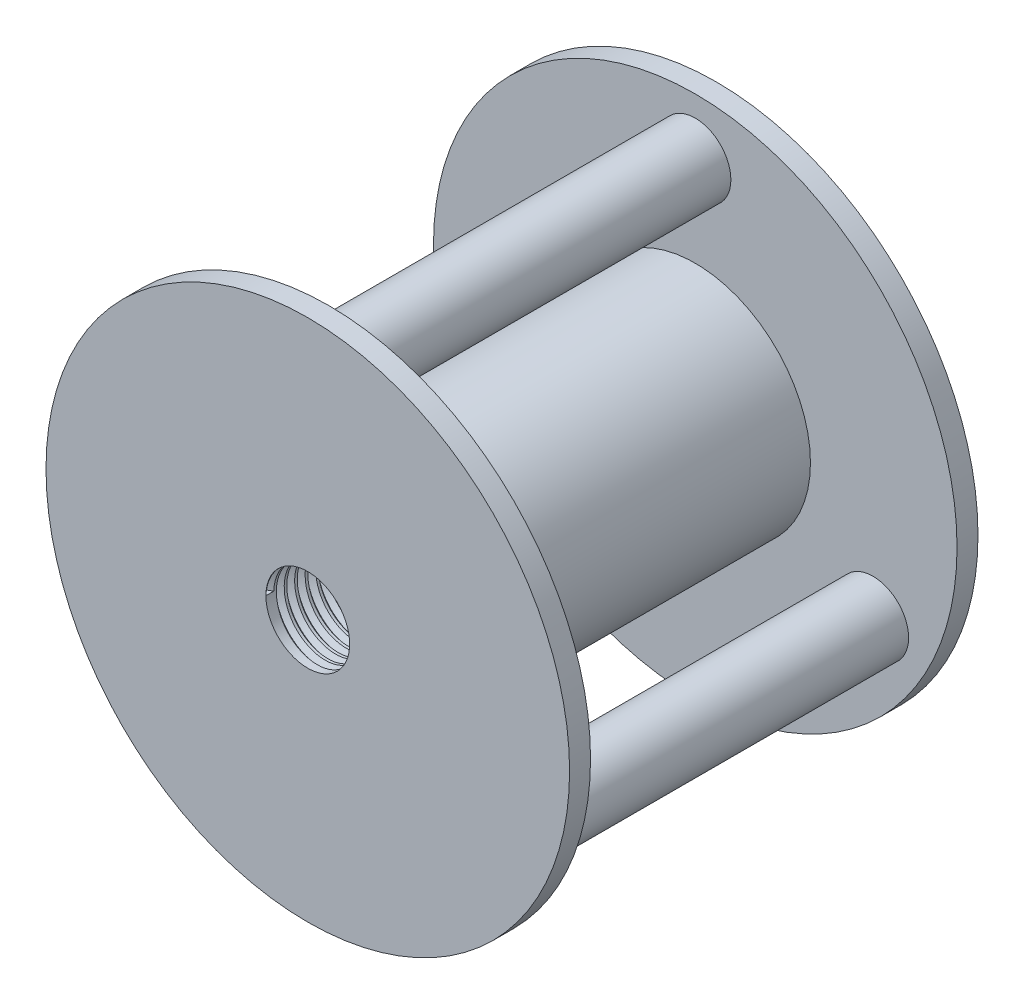
SolidWorks part; units mm, degrees
material "Plain Carbon Steel"
ref_plane "Front Plane" through (0, 0, 0) normal (1, 0, 0) x (0, 1, 0)
ref_plane "Top Plane" through (0, 0, 0) normal (0, 0, 1) x (0, 1, 0)
ref_plane "Right Plane" through (0, 0, 0) normal (0, 1, 0) x (-1, 0, 0)
sketch "Sketch1" plane through (0, 0, 0) normal (0, 0, 1) x (0, 1, 0)
  circle A0 centre (0, 0) radius 12.5
  dimension "D1" = 25
extrude "Boss-Extrude1" add sketch "Sketch1" along normal blind 1
sketch "Sketch2" plane through (0, 0, 1) normal (0, 0, 1) x (1, 0, 0)
  line L0 (0, 0) -> (0, 12.5) construction
  line L1 (0, 12.5) -> (0, 11.5) construction
  line L2 (0, 11.5) -> (0, 8.1) construction
  circle A0 centre (0, 0) radius 12.5 construction
  circle A1 centre (0, 9.8) radius 1.7
  circle A2 centre (8.487, -4.9) radius 1.7
  circle A3 centre (-8.487, -4.9) radius 1.7
  point P16 (0, 0)
  dimension "D3" = 3
  dimension "D1" = 1
  dimension "D2" = 3.4
extrude "Boss-Extrude2" add sketch "Sketch2" along normal blind 17.5
ref_plane "Plane1" through (0, 0, 9.75) normal (0, 0, 1) x (0, -1, 0)
sketch "Sketch3" plane through (0, 0, 1) normal (0, 0, 1) x (1, 0, 0)
  circle A0 centre (0, 0) radius 5.5
  dimension "D1" = 11
extrude "Boss-Extrude3" add sketch "Sketch3" along normal up to surface (8.75 mm away) up to plane "Plane1"
mirror "Mirror2" about plane through (0, 0, 9.75) normal (0, 0, 1) of "Boss-Extrude1", "Boss-Extrude3"
sketch "Sketch4" plane through (0, 0, 19.5) normal (0, 0, 1) x (1, 0, 0)
  circle A0 centre (0, 0) radius 2
  dimension "D1" = 4
extrude "Cut-Extrude1" cut sketch "Sketch4" against normal through all
thread "Thread1" pitch 0.5 method cut profile "Thread Profile1" start angle 0, offset 0, length 10, pitch 0.5, diameter 4
ref_plane "Plane2" through (-2, 0, 19.5) normal (0, -1, 0) x (-1, 0, 0)
sketch "Thread Profile1" plane through (-2, 0, 19.5) normal (0, -1, 0) x (-1, 0, 0)
  line L0 (0, 0) -> (0, 0.5) construction
  line L1 (0, 0) -> (0.2706, 0.1562)
  line L2 (0.2706, 0.1562) -> (0.2706, 0.2187)
  line L3 (0.2706, 0.2187) -> (0, 0.375)
  line L4 (0.2706, 0.1875) -> (0, 0.1875) construction
  line L11 (0, 0) -> (0, 0.375)
  point P2 (0, 0)
  dimension "Pitch" = 0.5
  dimension "Profile_Angle" = 60
  dimension "Profile_Land" = 0.0625
  dimension "Profile_Height" = 0.2706
thread "Thread2" pitch 0.5 method cut profile "Thread Profile2" start angle 0, offset 0, length 10, pitch 0.5, diameter 4
ref_plane "Plane3" through (2, 0, 0) normal (0, -1, 0) x (1, 0, 0)
sketch "Thread Profile2" plane through (2, 0, 0) normal (0, -1, 0) x (1, 0, 0)
  line L0 (0, 0) -> (0, 0.5) construction
  line L1 (0, 0) -> (0.2706, 0.1562)
  line L2 (0.2706, 0.1562) -> (0.2706, 0.2187)
  line L3 (0.2706, 0.2187) -> (0, 0.375)
  line L4 (0.2706, 0.1875) -> (0, 0.1875) construction
  line L11 (0, 0) -> (0, 0.375)
  point P2 (0, 0)
  dimension "Pitch" = 0.5
  dimension "Profile_Angle" = 60
  dimension "Profile_Land" = 0.0625
  dimension "Profile_Height" = 0.2706
